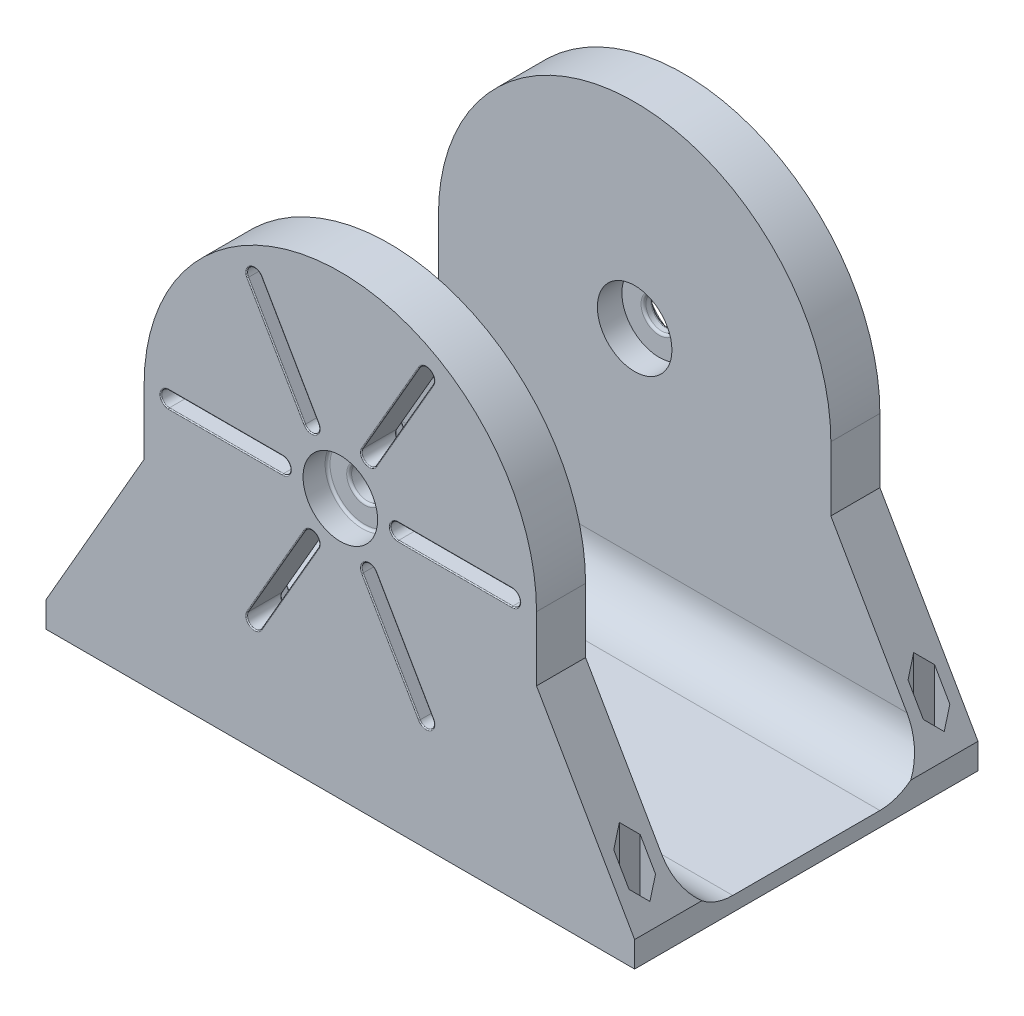
SolidWorks part; units mm, degrees
ref_plane "Front Plane" through (0, 0, 0) normal (0, 0, 1) x (1, 0, 0)
ref_plane "Top Plane" through (0, 0, 0) normal (0, 1, 0) x (1, 0, 0)
ref_plane "Right Plane" through (0, 0, 0) normal (1, 0, 0) x (0, 0, -1)
sketch "Sketch1" plane through (0, 0, 0) normal (0, 0, 1) x (1, 0, 0)
  line L0 (40, -13.1) -> (63, -53.1)
  line L2 (-40, 0) -> (-40, -13.1)
  line L3 (-40, -53.1) -> (40, -53.1)
  line L4 (40, 0) -> (40, -13.1)
  line L5 (63, -53.1) -> (40, -53.1)
  line L6 (-40, -13.1) -> (-63, -53.1)
  line L7 (-63, -53.1) -> (-40, -53.1)
  line L8 (-40, -13.1) -> (-40, -53.1) construction
  line L9 (40, -13.1) -> (40, -53.1) construction
  arc A0 (40, 0) -> (-40, 0) centre (0, 0) ccw
  dimension "D1" = 80
  dimension "D2" = 53.1
  dimension "D3" = 40
  dimension "D4" = 23
ref_plane "Plane1" through (0, 0, 25) normal (0, 0, 1) x (1, 0, 0)
ref_plane "Plane2" through (0, 0, -25) normal (0, 0, 1) x (1, 0, 0)
extrude "Boss-Extrude1" add sketch "Sketch1" along normal blind 10 from surface starting at plane "Plane1"
extrude "Boss-Extrude2" add sketch "Sketch1<2>" against normal blind 10 from surface separate body starting at plane "Plane2"
sketch "Sketch1<2>" plane through (0, 0, 0) normal (0, 0, 1) x (1, 0, 0) same geometry as "Sketch1"
sketch "Sketch2" plane through (0, 0, 0) normal (0, 0, 1) x (1, 0, 0)
  line L5 (-63, -53.1) -> (63, -53.1)
  line L6 (63, -53.1) -> (61.275, -50.1)
  line L7 (40, -13.1) -> (63, -53.1) construction
  line L8 (61.275, -50.1) -> (-61.275, -50.1)
  line L9 (-63, -53.1) -> (-40, -13.1) construction
  line L10 (-61.275, -50.1) -> (-63, -53.1)
  dimension "D1" = 3
extrude "Boss-Extrude3" add sketch "Sketch2" along normal up to next (25 mm away) and the other way up to next (25 mm away)
sketch "Sketch4" plane through (0, 0, 0) normal (0, 0, 1) x (1, 0, 0)
  circle A0 centre (0, 0) radius 3.2
  dimension "D1" = 6.4
extrude "Cut-Extrude1" cut sketch "Sketch4" against normal through all both and the other way through all
sketch "Sketch5" plane through (0, 0, 0) normal (0, 0, 1) x (1, 0, 0)
  line L0 (-33.2391, 3.05) -> (-10, 3.05)
  line L1 (-32.3586, 1.525) -> (-33.2391, 3.05) construction
  line L2 (-33.2391, 3.05) -> (-36.7609, 3.05)
  line L3 (-36.7609, 3.05) -> (-38.5218, 0)
  line L4 (-38.5218, 0) -> (-36.7609, -3.05)
  line L5 (-36.7609, -3.05) -> (-33.2391, -3.05)
  line L6 (-33.2391, -3.05) -> (-32.3586, -1.525) construction
  line L7 (-33.2391, -3.05) -> (-10, -3.05)
  line L8 (-10, 3.05) -> (-8.2391, 0)
  line L9 (-8.2391, 0) -> (-10, -3.05)
  line L10 (-31.4782, 0) -> (-32.3586, 1.525) construction
  line L11 (-32.3586, -1.525) -> (-31.4782, 0) construction
  arc A0 (-34.8671, 3.0471) -> (-32.3586, 1.525) centre (-35, 0) ccw construction
  circle A1 centre (0, 0) radius 35 construction
  arc A2 (-32.3586, 1.525) -> (-34.8671, 3.0471) centre (-35, 0) ccw construction
  circle A3 centre (-11.7609, 0) radius 3.05 construction
  point P8 (0, 0)
  dimension "D1" = 70
  dimension "D2" = 6.1
  dimension "D3" = 10
sketch "Sketch6" plane through (0, 0, 0) normal (0, 0, 1) x (1, 0, 0)
  line L0 (-35, 0) -> (-11.7609, 0) construction
  line L1 (-35, 1.5875) -> (-11.7609, 1.5875)
  line L2 (-35, -1.5875) -> (-11.7609, -1.5875)
  arc A0 (-35, 1.5875) -> (-35, -1.5875) centre (-35, 0) ccw
  arc A1 (-11.7609, -1.5875) -> (-11.7609, 1.5875) centre (-11.7609, 0) ccw
  point P4 (-23.3805, 0)
  point P9 (0, 0)
  point P10 (0, 0)
  point P11 (0, 0)
  dimension "D1" = 1.5875
extrude "Cut-Extrude4" cut sketch "Sketch5" along normal blind 2.8575 from surface starting at face at (3.2, 0, 25)
extrude "Cut-Extrude5" cut sketch "Sketch6" along normal up to next from surface starting at face at (-23.3805, 0, 25)
fillet "Fillet1" radius 0.2 26 edges at (-23.3805, -3.05, 25) (-23.3805, 3.05, 25) (-10.1734, 0, 35) (-23.3805, 1.5875, 35) (-36.5875, 0, 35) (-36.7609, 3.05, 26.4288) (-37.6414, 1.525, 25) (-36.7609, -3.05, 26.4288) (-38.5218, 0, 26.4288) (-37.6414, -1.525, 25) (-23.3805, -1.5875, 35) (-23.3805, -1.5875, 27.8575) (-36.5875, 0, 27.8575) (-23.3805, 1.5875, 27.8575) (-10.1734, 0, 27.8575) (-23.3805, 3.05, 27.8575) (-37.6414, 1.525, 27.8575) (-37.6414, -1.525, 27.8575) (-23.3805, -3.05, 27.8575) (-9.1195, -1.525, 27.8575) (-10, -3.05, 26.4288) (-9.1195, -1.525, 25) (-10, 3.05, 26.4288) (-9.1195, 1.525, 27.8575) (-8.2391, 0, 26.4288) (-9.1195, 1.525, 25)
pattern_circular "CirPattern1" count 6 over 360 about axis through (0, 0, 35) along (0, 0, -1) of "Cut-Extrude4", "Cut-Extrude5", "Fillet1"
sketch "Sketch8" plane through (0, 0, 0) normal (0, 0, 1) x (1, 0, 0)
  circle A0 centre (0, 0) radius 7.6
  dimension "D1" = 15.2
extrude "Cut-Extrude6" cut sketch "Sketch8" against normal blind 5 from surface starting at face at (-11.6902, -20.2481, 35)
extrude "Cut-Extrude7" cut sketch "Sketch8<2>" against normal blind 5 from surface starting at face at (3.2, 0, -25)
sketch "Sketch8<2>" plane through (0, 0, 0) normal (0, 0, 1) x (1, 0, 0) same geometry as "Sketch8"
sketch "Sketch10" plane through (0, 0, -35) normal (0, 0, -1) x (-1, 0, 0)
  line L0 (-14.3953, -5.9991) -> (-14.3953, 14.0234)
  line L1 (-14.3953, 14.0234) -> (-13.3642, 15.0075)
  line L2 (-10.8024, 16.9451) -> (-13.3642, 15.0075)
  line L3 (-10.8024, 16.9451) -> (-9.2024, 17.8657)
  line L4 (-9.2024, 17.8657) -> (-5.0253, 17.8657)
  line L5 (-5.0253, 17.8657) -> (-5.0253, 18.3079)
  line L6 (-4.4301, 18.9031) -> (6.9701, 18.9031)
  line L7 (7.5653, 18.3079) -> (7.5653, 17.8657)
  line L8 (7.5653, 17.8657) -> (9.2024, 17.8657)
  line L9 (9.2024, 17.8657) -> (10.8031, 16.9447)
  line L10 (10.8031, 16.9447) -> (13.371, 14.9429)
  line L11 (13.371, 14.9429) -> (14.3516, 14.0055)
  line L12 (14.3516, 14.0055) -> (14.3516, -6.1027)
  line L13 (-17.3953, -6.5718) -> (-17.3953, 15.3072)
  line L14 (-17.3953, 15.3072) -> (-15.3111, 17.2964)
  line L15 (-12.4619, 19.4514) -> (-15.3111, 17.2964)
  line L16 (-12.4619, 19.4514) -> (-10.6394, 20.5)
  line L17 (10.6394, 20.5) -> (12.4815, 19.4401)
  line L18 (12.4815, 19.4401) -> (15.3347, 17.2159)
  line L19 (15.3347, 17.2159) -> (17.3516, 15.288)
  line L20 (17.3516, 15.288) -> (17.3516, -6.6862)
  line L21 (-10.6394, 20.5) -> (10.6394, 20.5)
  arc A0 (-5.0253, 18.3079) -> (-4.4301, 18.9031) centre (-4.4301, 18.3079) cw
  arc A1 (6.9701, 18.9031) -> (7.5653, 18.3079) centre (6.9701, 18.3079) cw
  arc A2 (-14.3953, -5.9991) -> (14.3516, -6.1027) centre (0, 0) ccw
  arc A3 (-17.3953, -6.5718) -> (17.3516, -6.6862) centre (0, 0) ccw
  point P29 (0, 0)
  dimension "D1" = 15.5953
  dimension "D9" = 0.5952
  dimension "D16" = 0.5952
  dimension "D2" = 5.9991
  dimension "D3" = 20.0224
  dimension "D4" = 20.1082
  dimension "D5" = 1.3566
  dimension "D6" = 3.256
  dimension "D7" = 1.8467
  dimension "D8" = 1.6371
  dimension "D10" = 0.4422
  dimension "D11" = 11.4002
  dimension "D12" = 1.4253
  dimension "D13" = 3.212
  dimension "D14" = 1.846
  dimension "D15" = 4.1771
  dimension "D17" = 0.4422
  dimension "D18" = 0.9373
  dimension "D19" = 2.0018
  dimension "D20" = 0.921
  dimension "D21" = 0.9206
  dimension "D22" = 1.9376
  dimension "D23" = 2.8811
  dimension "D24" = 2.7902
  dimension "D25" = 3.6176
  dimension "D26" = 2.1253
  dimension "D27" = 3.5724
  dimension "D28" = 2.1026
  dimension "D29" = 21.2787
  dimension "D30" = 1.5969
  dimension "D31" = 21.879
  dimension "D32" = 21.9742
extrude "Boss-Extrude4" add sketch "Sketch10" along normal blind 5
sketch "Sketch11" plane through (0, 0, -35) normal (0, 0, -1) x (-1, 0, 0)
  circle A0 centre (0, 0) radius 7.5
  dimension "D1" = 15
extrude "Cut-Extrude8" cut sketch "Sketch11" against normal blind 3
sketch "Sketch12" plane through (0, 0, 0) normal (0, 1, 0) x (1, 0, 0)
  line L0 (40, -35) -> (40, -25) construction
  line L1 (-51.8823, 30) -> (-53.4412, 32.7)
  line L2 (-53.4412, 32.7) -> (-56.5588, 32.7)
  line L3 (-56.5588, 32.7) -> (-58.1177, 30)
  line L4 (-58.1177, 30) -> (-56.5588, 27.3)
  line L5 (-56.5588, 27.3) -> (-53.4412, 27.3)
  line L6 (-53.4412, 27.3) -> (-51.8823, 30)
  line L7 (58.1177, 30) -> (56.5588, 32.7)
  line L8 (56.5588, 32.7) -> (53.4412, 32.7)
  line L9 (53.4412, 32.7) -> (51.8823, 30)
  line L10 (51.8823, 30) -> (53.4412, 27.3)
  line L11 (53.4412, 27.3) -> (56.5588, 27.3)
  line L12 (56.5588, 27.3) -> (58.1177, 30)
  line L13 (56.5588, -32.7) -> (58.1177, -30)
  line L14 (58.1177, -30) -> (56.5588, -27.3)
  line L15 (56.5588, -27.3) -> (53.4412, -27.3)
  line L16 (53.4412, -27.3) -> (51.8823, -30)
  line L17 (51.8823, -30) -> (53.4412, -32.7)
  line L18 (53.4412, -32.7) -> (56.5588, -32.7)
  line L19 (-51.8823, -30) -> (-53.4412, -27.3)
  line L20 (-53.4412, -27.3) -> (-56.5588, -27.3)
  line L21 (-56.5588, -27.3) -> (-58.1177, -30)
  line L22 (-58.1177, -30) -> (-56.5588, -32.7)
  line L23 (-56.5588, -32.7) -> (-53.4412, -32.7)
  line L24 (-53.4412, -32.7) -> (-51.8823, -30)
  line L25 (55, -30) -> (-55, -30) construction
  line L26 (55, -30) -> (55, 30) construction
  line L27 (55, 30) -> (-55, 30) construction
  line L28 (-55, -30) -> (-55, 30) construction
  line L29 (55, -30) -> (-55, 30) construction
  line L30 (55, 30) -> (-55, -30) construction
  line L31 (40, 35) -> (40, 25) construction
  circle A0 centre (-55, 30) radius 2.7 construction
  circle A1 centre (55, 30) radius 2.7 construction
  circle A2 centre (55, -30) radius 2.7 construction
  circle A3 centre (-55, -30) radius 2.7 construction
  point P1 (56.9875, -31.2066)
  point P9 (0, 0)
  point P17 (-53.3597, -31.2066)
  point P25 (0, 0)
  point P33 (56.877, 31.2066)
  point P38 (-57.1007, -31.2066)
  point P39 (-51.737, 31.2066)
  point P40 (51.0798, 31.2066)
  point P41 (53.5038, -31.2066)
  point P44 (40, -30)
  point P47 (56.5392, -32.7113)
  point P48 (51.8823, -30)
  dimension "D1" = 110
  dimension "D2" = 15
  dimension "D3" = 5.4
sketch "Sketch13" plane through (0, 0, 0) normal (0, 1, 0) x (1, 0, 0)
  line L1 (-55, -30) -> (55, -30) construction
  line L2 (-55, -30) -> (-55, 30) construction
  line L3 (-55, 30) -> (55, 30) construction
  line L4 (55, -30) -> (55, 30) construction
  line L5 (-55, -30) -> (55, 30) construction
  line L6 (-55, 30) -> (55, -30) construction
  circle A0 centre (-55, 30) radius 1.4
  circle A1 centre (55, 30) radius 1.4
  circle A3 centre (55, -30) radius 1.4
  circle A4 centre (-55, -30) radius 1.4
  point P0 (0, 0)
  dimension "D1" = 2.8
extrude "Cut-Extrude11" cut sketch "Sketch12" against normal offset from surface (48.1 mm away) 2 up to face at (0, -50.1, 0)
extrude "Cut-Extrude12" cut sketch "Sketch13" against normal up to next
sketch "Sketch14" plane through (0, 0, 0) normal (0, 0, 1) x (1, 0, 0)
  line L0 (-63, -53.1) -> (-60, -47.8826)
  line L1 (-63, -53.1) -> (-40, -13.1) construction
  line L2 (-60, -47.8826) -> (-60, -53.1)
  line L3 (63, -53.1) -> (-63, -53.1) construction
  line L4 (-60, -53.1) -> (-63, -53.1)
  line L5 (60, -47.8826) -> (60, -53.1)
  line L6 (40, -13.1) -> (63, -53.1) construction
  line L7 (60, -53.1) -> (63, -53.1)
  line L8 (63, -53.1) -> (60, -47.8826)
  dimension "D1" = 3
extrude "Cut-Extrude13" cut sketch "Sketch14" against normal through all both and the other way through all
fillet "Fillet2" radius 0.5 6 edges at (3.2, 0, 25) (3.2, 0, 30) (7.6, 0, 30) (-7.5, 0, -32) (-3.2, 0, -32) (3.2, 0, -30)
fillet "Fillet3" radius 10 2 edges at (0, -50.1, 25) (0, -50.1, -25)
equation "\"w\" = 50mm"
equation "\"D1@Plane1\"=\"w\"/2"
equation "\"D1@Plane2\"=\"w\"/2"
equation "\"t\"= 10mm"
equation "\"D1@Boss-Extrude1\"=\"t\""
equation "\"D1@Boss-Extrude2\"=\"t\""
